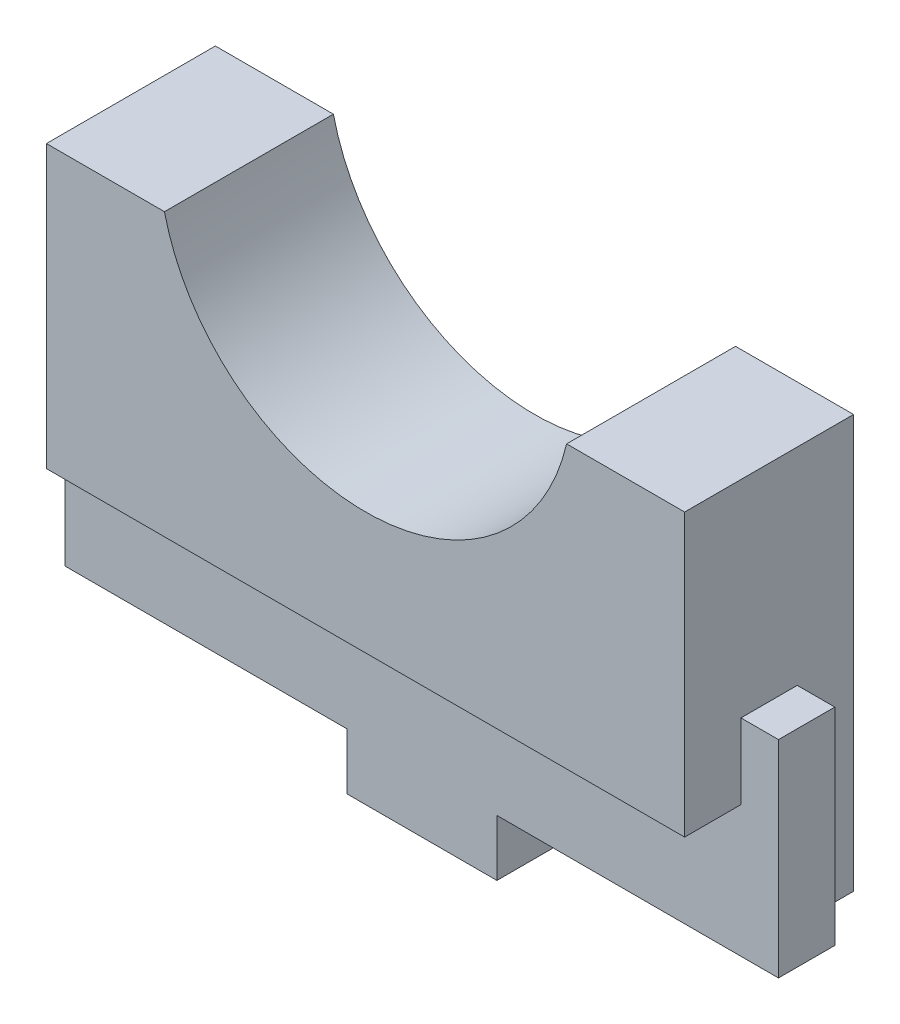
SolidWorks part; units mm, degrees
ref_plane "Front Plane" through (0, 0, 0) normal (0, 0, 1) x (1, 0, 0)
ref_plane "Top Plane" through (0, 0, 0) normal (0, 1, 0) x (1, 0, 0)
ref_plane "Right Plane" through (0, 0, 0) normal (1, 0, 0) x (0, 0, -1)
sketch "Sketch1" plane through (0, 0, 0) normal (0, 0, 1) x (1, 0, 0)
  line L0 (-17, 0) -> (17, 0) construction
  line L1 (0, 0) -> (0, -11) construction
  line L2 (-17, -2.5) -> (17, -2.5)
  line L4 (-17, -2.5) -> (-17, -24.5)
  line L5 (-17, -24.5) -> (17, -24.5)
  line L6 (17, -24.5) -> (17, -2.5)
  circle A0 centre (0, 0) radius 11
  dimension "D1" = 22
  dimension "D2" = 17
  dimension "D5" = 22
  dimension "D3" = 2.5
extrude "Boss-Extrude1" add sketch "Sketch1" along normal blind 9 contours A0 L2 L4 L5 L6 region at (0, -15.1497, 0)
sketch "Sketch2" plane through (0, -24.5, 0) normal (0, -1, 0) x (1, 0, 0)
  line L1 (4, 0) -> (-4, 0)
  line L3 (4, 9) -> (-4, 9)
  line L4 (-4, 0) -> (-4, 9)
  line L5 (-17, 9) -> (17, 9) construction
  line L6 (4, 0) -> (4, 9)
  dimension "D1" = 8
  dimension "D2" = 9
  dimension "D3" = 4
  dimension "D4" = 4
extrude "Boss-Extrude2" add sketch "Sketch2" along normal blind 3
sketch "Sketch3" plane through (-17, 0, 0) normal (-1, 0, 0) x (0, 0, 1)
  line L0 (9, -24.5) -> (0, -24.5) construction
  line L1 (0, -2.5) -> (0, -24.5) construction
  line L7 (6, -13.5) -> (3, -13.5)
  line L8 (6, -13.5) -> (6, -24.5)
  line L9 (6, -24.5) -> (3, -24.5)
  line L10 (3, -13.5) -> (3, -24.5)
  line L11 (6, -13.5) -> (3, -24.5) construction
  line L12 (6, -24.5) -> (3, -13.5) construction
  point P12 (4.3664, -11.5604)
  dimension "D1" = 11
  dimension "D2" = 3
  dimension "D3" = 3
  dimension "D4" = 11
  dimension "D5" = 3
extrude "Boss-Extrude3" add sketch "Sketch3" along normal blind 2
sketch "Sketch4" plane through (17, 0, 0) normal (1, 0, 0) x (0, 0, -1)
  line L0 (0, -24.5) -> (0, -2.5) construction
  line L1 (-6, -13.5) -> (-3, -13.5)
  line L2 (-6, -13.5) -> (-6, -24.5)
  line L3 (-6, -24.5) -> (-3, -24.5)
  line L4 (-3, -13.5) -> (-3, -24.5)
  line L5 (-6, -13.5) -> (-3, -24.5) construction
  line L6 (-6, -24.5) -> (-3, -13.5) construction
  line L7 (-9, -24.5) -> (0, -24.5) construction
  point P0 (-4.5, -19)
  dimension "D1" = 3
  dimension "D2" = 3
  dimension "D3" = 11
extrude "Boss-Extrude4" add sketch "Sketch4" along normal blind 2
sketch "Sketch5" plane through (0, 0, 0) normal (0, 0, -1) x (-1, 0, 0)
  line L0 (17, -2.5) -> (17, -24.5) construction
  line L1 (-17, -27.5) -> (17, -27.5)
  line L2 (-17, -27.5) -> (-17, -17.5)
  line L3 (-17, -17.5) -> (17, -17.5)
  line L4 (17, -27.5) -> (17, -17.5)
  dimension "D1" = 10
sketch "Sketch6" plane through (0, 0, 9) normal (0, 0, 1) x (1, 0, 0)
  line L0 (17, -24.5) -> (17, -2.5) construction
  line L1 (-17, -27.5) -> (17, -27.5)
  line L2 (-17, -27.5) -> (-17, -17.5)
  line L3 (-17, -17.5) -> (17, -17.5)
  line L4 (17, -27.5) -> (17, -17.5)
  dimension "D1" = 10
  dimension "D2" = 34
extrude "Cut-Extrude2" cut sketch "Sketch6" against normal blind 3
